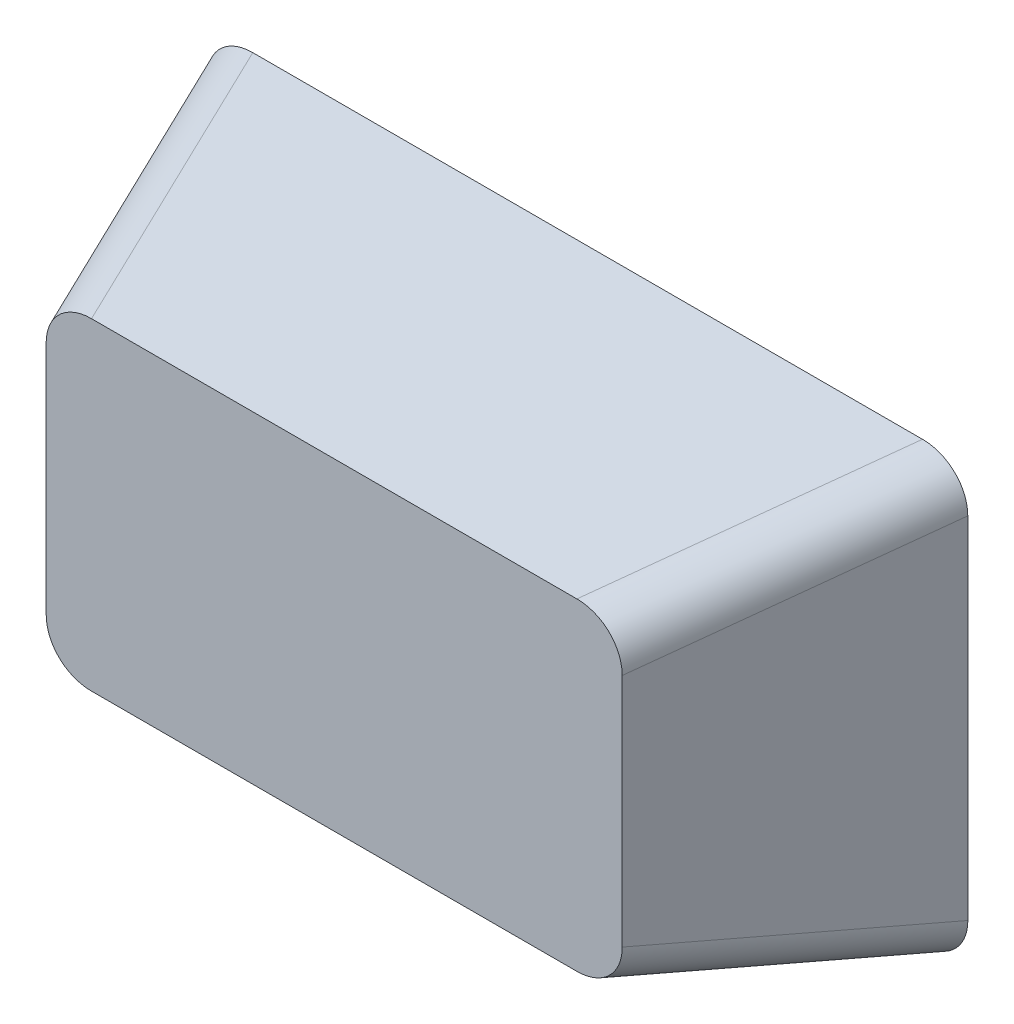
SolidWorks part; units mm, degrees
ref_plane "Front Plane" through (0, 0, 0) normal (0, 0, 1) x (1, 0, 0)
ref_plane "Top Plane" through (0, 0, 0) normal (0, 1, 0) x (1, 0, 0)
ref_plane "Right Plane" through (0, 0, 0) normal (1, 0, 0) x (0, 0, -1)
sketch "Sketch3" plane through (0, 0, 0) normal (0, 0, 1) x (1, 0, 0)
  line L1 (62.5, -35) -> (-62.5, -35)
  line L2 (62.5, -35) -> (62.5, 35)
  line L3 (62.5, 35) -> (-62.5, 35)
  line L4 (-62.5, -35) -> (-62.5, 35)
  line L5 (62.5, -35) -> (-62.5, 35) construction
  line L6 (62.5, 35) -> (-62.5, -35) construction
  point P0 (0, 0)
  dimension "D1" = 125
  dimension "D2" = 70
ref_plane "Plane1" through (0, 0, -55) normal (0, 0, 1) x (1, 0, 0)
sketch "Sketch4" plane through (0, 0, -55) normal (0, 0, 1) x (1, 0, 0)
  line L1 (82.5, -47.5) -> (-82.5, -47.5)
  line L2 (82.5, -47.5) -> (82.5, 47.5)
  line L3 (82.5, 47.5) -> (-82.5, 47.5)
  line L4 (-82.5, -47.5) -> (-82.5, 47.5)
  line L5 (82.5, -47.5) -> (-82.5, 47.5) construction
  line L6 (82.5, 47.5) -> (-82.5, -47.5) construction
  point P0 (0, 0)
  dimension "D1" = 165
  dimension "D2" = 95
loft "Loft1" add profiles "Sketch3", "Sketch4" connector at (-62.5, -35, 0) connector at (-82.5, -47.5, -55)
ref_plane "Plane2" through (0, 0, -27.5) normal (0, 0, 1) x (1, 0, 0)
sketch "Sketch5" plane through (0, 0, -27.5) normal (0, 0, 1) x (1, 0, 0)
  line L1 (22.5, -12.5) -> (-22.5, -12.5)
  line L2 (22.5, -12.5) -> (22.5, 12.5)
  line L3 (22.5, 12.5) -> (-22.5, 12.5)
  line L4 (-22.5, -12.5) -> (-22.5, 12.5)
  line L5 (22.5, -12.5) -> (-22.5, 12.5) construction
  line L6 (22.5, 12.5) -> (-22.5, -12.5) construction
  point P0 (0, 0)
  dimension "D1" = 45
  dimension "D2" = 25
sketch "Sketch7" plane through (0, 0, -55) normal (0, 0, 1) x (1, 0, 0)
  line L0 (82.5, -47.5) -> (82.5, 47.5) construction
  line L5 (77.5, -42.5) -> (-77.5, -42.5)
  line L6 (77.5, -42.5) -> (77.5, 42.5)
  line L11 (77.5, 42.5) -> (-77.5, 42.5)
  line L12 (-77.5, -42.5) -> (-77.5, 42.5)
  line L13 (77.5, -42.5) -> (-77.5, 42.5) construction
  line L14 (77.5, 42.5) -> (-77.5, -42.5) construction
  line L15 (82.5, 47.5) -> (-82.5, 47.5) construction
  point P0 (0, 0)
  point P1 (0, 0)
  point P7 (0, 0)
  dimension "D1" = 5
  dimension "D2" = 5
loft "Cut-Loft2" cut profiles "Sketch7", "Sketch5" connector at (-77.5, -42.5, -55) connector at (-22.5, -12.5, -27.5)
fillet "Fillet1" radius 10 4 edges
